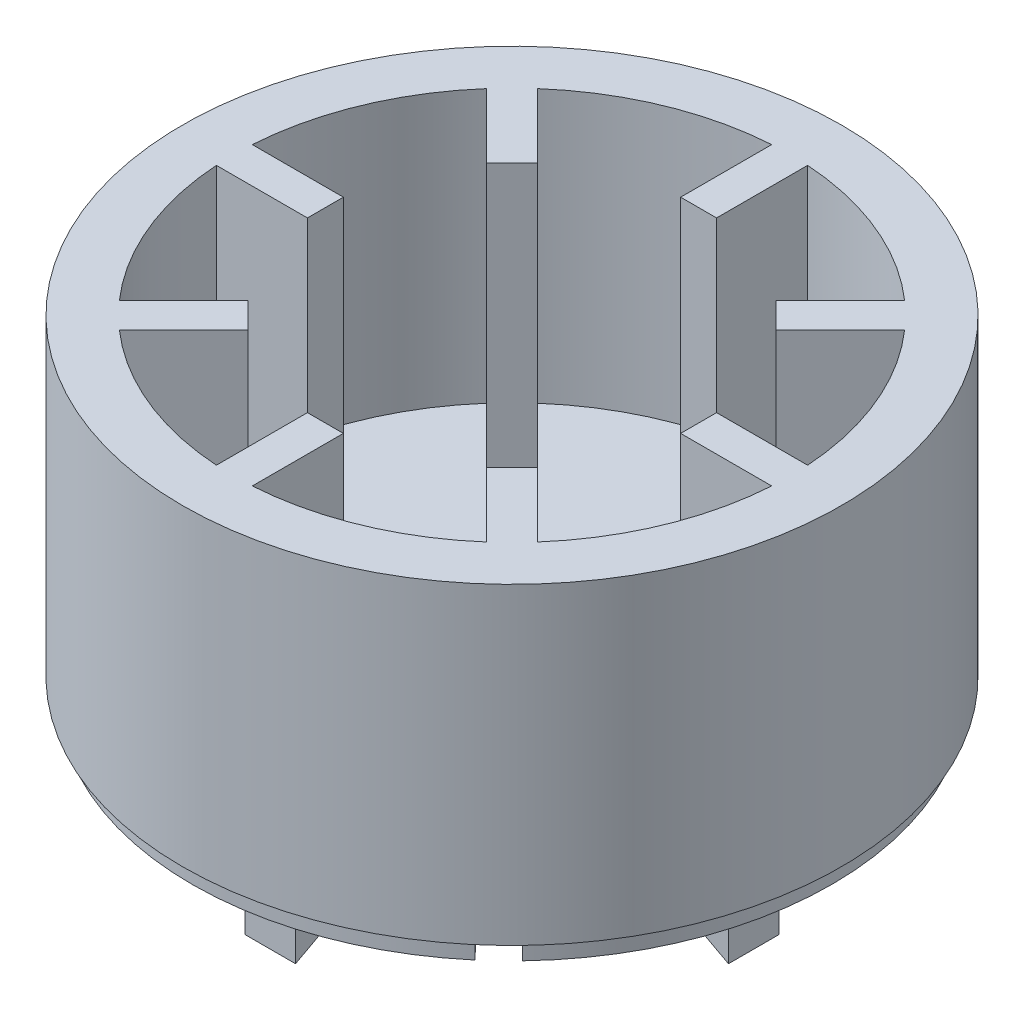
SolidWorks part; units mm, degrees
ref_plane "Front Plane" through (0, 0, 0) normal (0, 0, 1) x (1, 0, 0)
ref_plane "Top Plane" through (0, 0, 0) normal (0, 1, 0) x (1, 0, 0)
ref_plane "Right Plane" through (0, 0, 0) normal (1, 0, 0) x (0, 0, -1)
sketch "Sketch1" plane through (0, 0, 0) normal (0, 1, 0) x (1, 0, 0)
  circle A0 centre (0, 0) radius 8.345
  circle A1 centre (0, 0) radius 7.045
  dimension "D1" = 16.69
  dimension "D2" = 1.3
extrude "Boss-Extrude1" add sketch "Sketch1" along normal blind 7.92
sketch "Sketch2" plane through (0, 0, 0) normal (0, 1, 0) x (1, 0, 0)
  circle A0 centre (0, 0) radius 7.045
  dimension "D1" = 14.09
extrude "Boss-Extrude2" add sketch "Sketch2" along normal blind 1.02
sketch "Sketch3" plane through (0, 7.92, 0) normal (0, 1, 0) x (1, 0, 0)
  line L0 (0, 10.0641) -> (0, 8.345) construction
  line L1 (-11.9221, 0) -> (13.1994, 0) construction
  line L7 (-0.455, 4.725) -> (0.455, 4.725)
  line L8 (0.455, 4.725) -> (0.455, 8.3326)
  line L9 (-0.455, 4.725) -> (-0.455, 8.3326)
  line L10 (0, 4.725) -> (0, -10.6447) construction
  line L11 (3.0193, 3.6628) -> (5.5703, 6.2138)
  line L12 (3.6628, 3.0193) -> (6.2138, 5.5703)
  line L13 (3.0193, 3.6628) -> (3.6628, 3.0193)
  line L14 (4.725, 0.455) -> (8.3326, 0.455)
  line L15 (4.725, -0.455) -> (8.3326, -0.455)
  line L16 (4.725, 0.455) -> (4.725, -0.455)
  line L17 (3.6628, -3.0193) -> (6.2138, -5.5703)
  line L18 (3.0193, -3.6628) -> (5.5703, -6.2138)
  line L19 (3.6628, -3.0193) -> (3.0193, -3.6628)
  line L20 (0.455, -4.725) -> (0.455, -8.3326)
  line L21 (-0.455, -4.725) -> (-0.455, -8.3326)
  line L22 (0.455, -4.725) -> (-0.455, -4.725)
  line L23 (-3.0193, -3.6628) -> (-5.5703, -6.2138)
  line L24 (-3.6628, -3.0193) -> (-6.2138, -5.5703)
  line L25 (-3.0193, -3.6628) -> (-3.6628, -3.0193)
  line L26 (-4.725, -0.455) -> (-8.3326, -0.455)
  line L27 (-4.725, 0.455) -> (-8.3326, 0.455)
  line L28 (-4.725, -0.455) -> (-4.725, 0.455)
  line L29 (-3.6628, 3.0193) -> (-6.2138, 5.5703)
  line L30 (-3.0193, 3.6628) -> (-5.5703, 6.2138)
  line L31 (-3.6628, 3.0193) -> (-3.0193, 3.6628)
  circle A0 centre (0, 0) radius 8.345 construction
  arc A1 (-0.455, 8.3326) -> (0.455, 8.3326) centre (0, 0) cw
  arc A2 (5.5703, 6.2138) -> (6.2138, 5.5703) centre (0, 0) cw
  arc A3 (8.3326, 0.455) -> (8.3326, -0.455) centre (0, 0) cw
  arc A4 (6.2138, -5.5703) -> (5.5703, -6.2138) centre (0, 0) cw
  arc A5 (0.455, -8.3326) -> (-0.455, -8.3326) centre (0, 0) cw
  arc A6 (-5.5703, -6.2138) -> (-6.2138, -5.5703) centre (0, 0) cw
  arc A7 (-8.3326, -0.455) -> (-8.3326, 0.455) centre (0, 0) cw
  arc A8 (-6.2138, 5.5703) -> (-5.5703, 6.2138) centre (0, 0) cw
  point P49 (0, 0)
  dimension "D3" = 8
extrude "Boss-Extrude3" add sketch "Sketch3" against normal through all
sketch "Sketch4" plane through (0, 0, 0) normal (0, -1, 0) x (1, 0, 0)
  line L1 (5.8574, 5.5961) -> (2.9273, 2.4868)
  line L2 (5.2388, 6.1791) -> (2.3087, 3.0697)
  line L3 (5.8574, 5.5961) -> (5.2388, 6.1791)
  line L4 (-5.5961, 5.8574) -> (-6.1791, 5.2388)
  line L5 (-5.5961, 5.8574) -> (-2.4868, 2.9273)
  line L6 (-6.1791, 5.2388) -> (-3.0697, 2.3087)
  line L9 (5.5961, -5.8574) -> (2.4868, -2.9273)
  line L10 (6.1791, -5.2388) -> (3.0697, -2.3087)
  line L11 (5.5961, -5.8574) -> (6.1791, -5.2388)
  line L13 (-5.8574, -5.5961) -> (-2.9273, -2.4868)
  line L14 (-5.2388, -6.1791) -> (-2.3087, -3.0697)
  line L15 (-5.8574, -5.5961) -> (-5.2388, -6.1791)
  circle A0 centre (0, 0) radius 3.841
  circle A1 centre (0, 0) radius 8.101
  point P23 (0, 0)
  dimension "D1" = 4.26
  dimension "D4" = 7.682
  dimension "D2" = 0.85
  dimension "D3" = 4
extrude "Boss-Extrude4" add sketch "Sketch4" along normal blind 0.51 contours L6 A1 L13 A0 | L2 A1 L5 A0 | L10 A1 L1 A0 | L14 A1 L9 A0 region at (5.7245, 0, 0.17) region at (-0.17, 0, 5.7245) region at (-5.7245, 0, -0.17) region at (0.17, 0, -5.7245)
sketch "Sketch5" plane through (0, -0.51, 0) normal (0, -1, 0) x (1, 0, 0)
  line L0 (0, 9.0373) -> (0, -9.0149) construction
  line L1 (-9.2615, 0) -> (9.127, 0) construction
  line L2 (0.64, 3.841) -> (-0.64, 3.841)
  line L3 (-0.64, 3.841) -> (-0.64, 6.121)
  line L4 (-0.64, 6.121) -> (0.64, 6.121)
  line L5 (0.64, 3.841) -> (0.64, 6.121)
  line L6 (3.841, 0.64) -> (6.121, 0.64)
  line L7 (6.121, 0.64) -> (6.121, -0.64)
  line L8 (3.841, -0.64) -> (6.121, -0.64)
  line L9 (3.841, -0.64) -> (3.841, 0.64)
  line L10 (0.64, -3.841) -> (0.64, -6.121)
  line L11 (0.64, -6.121) -> (-0.64, -6.121)
  line L12 (-0.64, -3.841) -> (-0.64, -6.121)
  line L13 (-0.64, -3.841) -> (0.64, -3.841)
  line L14 (-3.841, -0.64) -> (-6.121, -0.64)
  line L15 (-6.121, -0.64) -> (-6.121, 0.64)
  line L16 (-3.841, 0.64) -> (-6.121, 0.64)
  line L17 (-3.841, 0.64) -> (-3.841, -0.64)
  point P10 (0, 3.841)
  point P11 (0, 6.121)
  point P26 (0, 0)
  dimension "D3" = 3.841
  dimension "D1" = 0.64
  dimension "D2" = 2.28
  dimension "D4" = 4
extrude "Boss-Extrude5" add sketch "Sketch5" along normal blind 2.41
sketch "Sketch6" plane through (0, 0, -0.64) normal (0, 0, -1) x (-1, 0, 0)
  line L0 (3.841, -0.51) -> (3.841, -1.7)
  line L1 (3.841, -2.92) -> (3.841, -0.51) construction
  line L2 (3.841, -1.7) -> (6.121, -2.92)
  line L3 (6.121, -2.92) -> (3.841, -2.92)
  line L4 (3.841, -2.92) -> (3.841, -1.7)
  line L5 (-3.841, -0.51) -> (-3.841, -1.7)
  line L6 (-3.841, -2.92) -> (-3.841, -0.51) construction
  line L7 (-3.841, -1.7) -> (-6.121, -2.92)
  line L8 (-6.121, -2.92) -> (-3.841, -2.92)
  line L9 (-3.841, -2.92) -> (-3.841, -1.7)
  line M2 (3.841, -0.51) -> (3.841, -2.92)
  line M3 (3.841, -2.92) -> (6.121, -2.92)
  dimension "D1" = 1.19
  dimension "D2" = 1.19
extrude "Cut-Extrude1" cut sketch "Sketch6" against normal through all contours L2 M2 M3 region at (-4.601, -2.5133, -0.64)
sketch "Sketch7" plane through (0.64, 0, 0) normal (1, 0, 0) x (0, 0, -1)
  line L0 (3.841, -0.51) -> (3.841, -1.7)
  line L1 (3.841, -2.92) -> (3.841, -0.51) construction
  line L2 (-3.841, -0.51) -> (-3.841, -1.7)
  line L3 (-3.841, -2.92) -> (-3.841, -0.51) construction
  line L4 (3.841, -1.7) -> (6.121, -2.92)
  line L5 (6.121, -2.92) -> (3.841, -2.92)
  line L6 (3.841, -2.92) -> (3.841, -1.7)
  line L7 (-3.841, -1.7) -> (-6.121, -2.92)
  line L8 (-6.121, -2.92) -> (-3.841, -2.92)
  line L9 (-3.841, -2.92) -> (-3.841, -1.7)
  line M2 (3.841, -0.51) -> (3.841, -2.92)
  line M3 (3.841, -2.92) -> (6.121, -2.92)
  dimension "D1" = 1.19
  dimension "D2" = 1.19
extrude "Cut-Extrude2" cut sketch "Sketch7" against normal blind 2.41 contours L4 M2 M3 | L8 L9 L7 region at (0.64, -2.5133, -4.601) region at (0.64, -2.5133, 4.601)
extrude "Cut-Extrude3" cut sketch "Sketch6<3>" against normal blind 2.41 contours L8 L9 L7 region at (4.601, -2.5133, -0.64)
sketch "Sketch6<3>" plane through (0, 0, -0.64) normal (0, 0, -1) x (-1, 0, 0) same geometry as "Sketch6"
